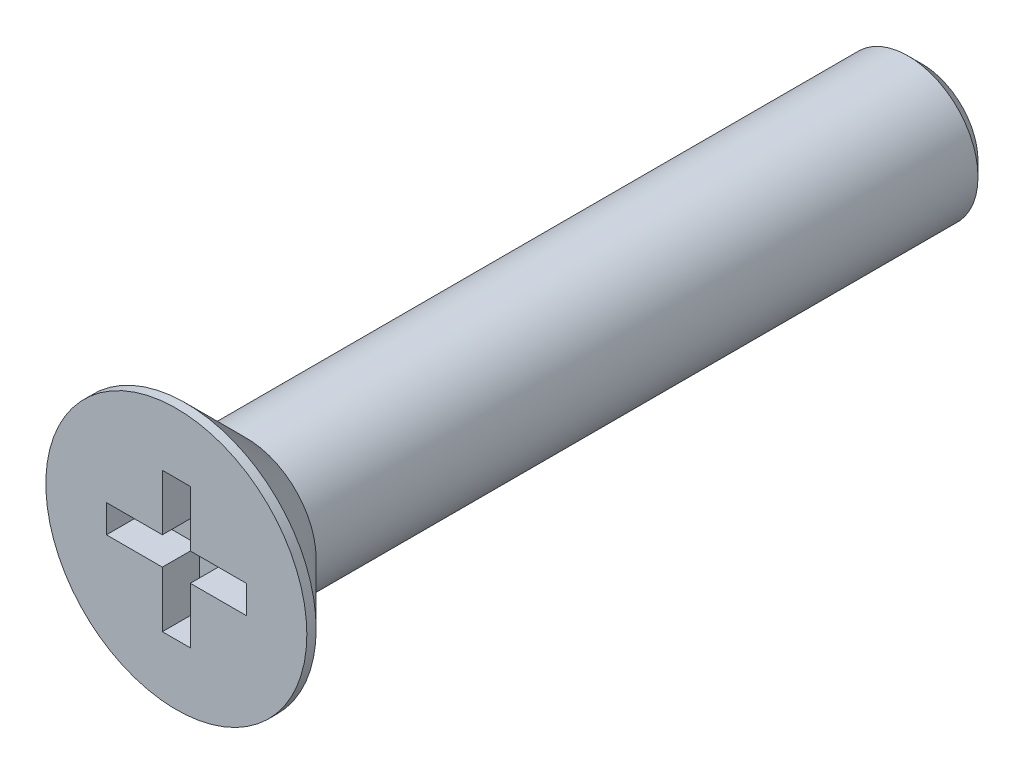
SolidWorks part; units mm, degrees
ref_plane "Ebene vorne" through (0, 0, 0) normal (0, 0, 1) x (1, 0, 0)
ref_plane "Ebene oben" through (0, 0, 0) normal (0, 1, 0) x (1, 0, 0)
ref_plane "Ebene rechts" through (0, 0, 0) normal (1, 0, 0) x (0, 0, -1)
sketch "Skizze1" plane through (0, 0, 0) normal (1, 0, 0) x (0, 0, -1)
  line L0 (-31.7636, 0) -> (42.9935, 0) construction
  line L1 (0, 26.0256) -> (0, -29.3045) construction
  line L2 (0, 0) -> (0, 2.8)
  line L3 (0.2, 2.8) -> (1.5, 1.5)
  line L4 (1.5, 1.5) -> (16, 1.5)
  line L5 (16, 1.5) -> (16, 0)
  line L6 (16, 0) -> (0, 0)
  line L7 (0, 2.8) -> (0.2, 2.8)
  dimension "D1" = 3
  dimension "D2" = 16
  dimension "D3" = 5.6
  dimension "D4" = 45
  dimension "D5" = 1.5
  dimension "D6" = 0.2
revolve "Rotation1" add sketch "Skizze1" angle 360 about L0
sketch "Skizze3" plane through (0, 0, 0) normal (0, 0, 1) x (1, 0, 0)
  line L0 (0, 1.5356) -> (0, -1.3958) construction
  line L1 (-1.5297, 0) -> (1.3792, 0) construction
  line L2 (-1.5, -0.3) -> (-1.5, 0.3)
  line L3 (-1.5, 0.3) -> (-0.3, 0.3)
  line L4 (-0.3, 0.3) -> (-0.3, 1.5)
  line L5 (-0.3, 1.5) -> (0.3, 1.5)
  line L6 (0.3, 0.3) -> (0.3, 1.5)
  line L7 (1.5, 0.3) -> (0.3, 0.3)
  line L8 (1.5, -0.3) -> (1.5, 0.3)
  line L9 (1.5, -0.3) -> (0.3, -0.3)
  line L10 (0.3, -0.3) -> (0.3, -1.5)
  line L11 (-0.3, -1.5) -> (0.3, -1.5)
  line L12 (-0.3, -0.3) -> (-0.3, -1.5)
  line L13 (-1.5, -0.3) -> (-0.3, -0.3)
  point P11 (0, 1.5)
  point P14 (0, -1.5)
  point P16 (1.5, 0)
  point P21 (-1.5, 0)
  dimension "D1" = 0.6
  dimension "D2" = 3
extrude "Schnitt-Linear austragen1" cut sketch "Skizze3" against normal blind 0.8
chamfer "Fase1" distance 0.3 angle 45 1 edges at (1.5, 0, -16)
ref_axis "Achse1" through (0, 0, 0.3) along (0, 0, -1)
